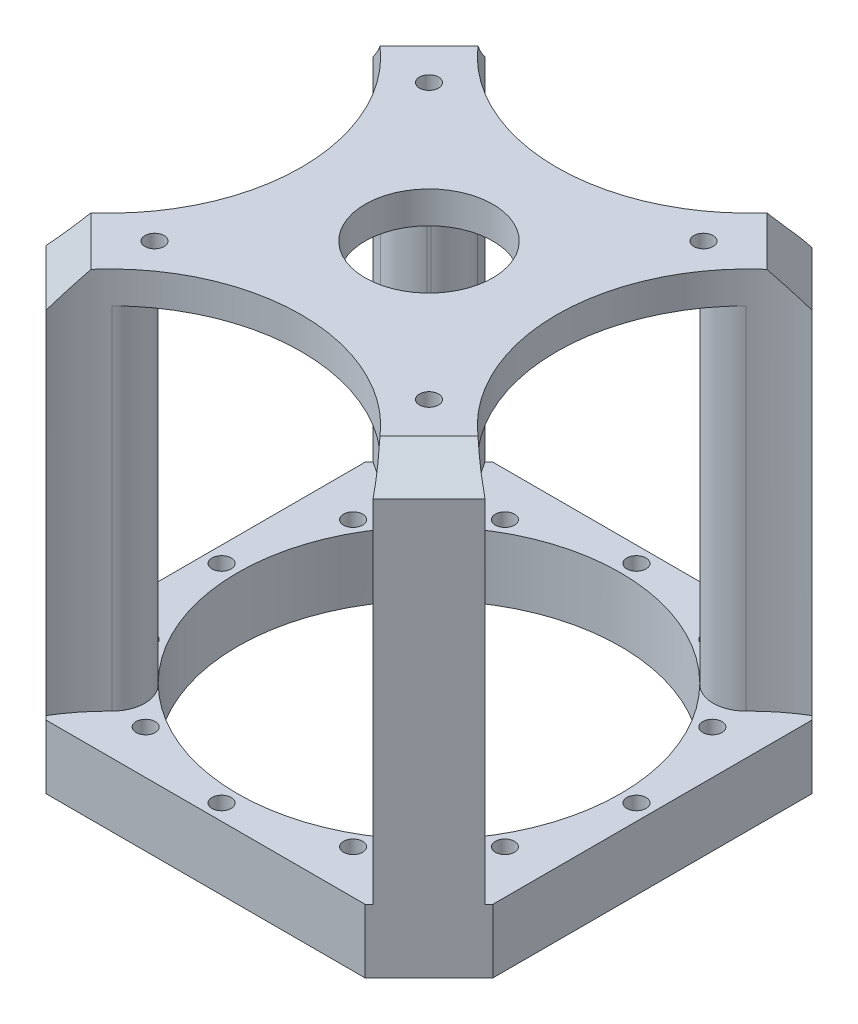
SolidWorks part; units mm, degrees
ref_plane "Front Plane" through (0, 0, 0) normal (0, 0, 1) x (1, 0, 0)
ref_plane "Top Plane" through (0, 0, 0) normal (0, 1, 0) x (1, 0, 0)
ref_plane "Right Plane" through (0, 0, 0) normal (1, 0, 0) x (0, 0, -1)
sketch "Sketch1" plane through (0, 0, 0) normal (0, 1, 0) x (1, 0, 0)
  line L1 (-35, -35) -> (35, -35)
  line L2 (-35, -35) -> (-35, 35)
  line L3 (-35, 35) -> (35, 35)
  line L4 (35, -35) -> (35, 35)
  line L5 (-35, -35) -> (35, 35) construction
  line L6 (-35, 35) -> (35, -35) construction
  circle A0 centre (0, 0) radius 35 construction
  circle A1 centre (0, 0) radius 30
  circle A2 centre (0, 0) radius 32.5 construction
  circle A3 centre (0, 32.5) radius 1.5
  circle A4 centre (16.25, 28.1458) radius 1.5
  circle A5 centre (28.1458, 16.25) radius 1.5
  circle A6 centre (32.5, 0) radius 1.5
  circle A7 centre (28.1458, -16.25) radius 1.5
  circle A8 centre (16.25, -28.1458) radius 1.5
  circle A9 centre (0, -32.5) radius 1.5
  circle A10 centre (-16.25, -28.1458) radius 1.5
  circle A11 centre (-28.1458, -16.25) radius 1.5
  circle A12 centre (-32.5, 0) radius 1.5
  circle A13 centre (-28.1458, 16.25) radius 1.5
  circle A14 centre (-16.25, 28.1458) radius 1.5
  point P35 (0, 0)
  dimension "D1" = 70
  dimension "D2" = 60
  dimension "D3" = 65
  dimension "D4" = 3
  dimension "D5" = 12
extrude "Boss-Extrude1" add sketch "Sketch1" along normal blind 65
sketch "Sketch2" plane through (0, 65, 0) normal (0, 1, 0) x (1, 0, 0)
  line L1 (-35, -35) -> (35, -35)
  line L2 (-35, -35) -> (-35, 35)
  line L3 (-35, 35) -> (35, 35)
  line L4 (35, -35) -> (35, 35)
  line L5 (-35, -35) -> (35, 35) construction
  line L6 (-35, 35) -> (35, -35) construction
  line L7 (-21.5, -21.5) -> (21.5, -21.5) construction
  line L8 (-21.5, -21.5) -> (-21.5, 21.5) construction
  line L9 (-21.5, 21.5) -> (21.5, 21.5) construction
  line L10 (21.5, -21.5) -> (21.5, 21.5) construction
  line L11 (-21.5, -21.5) -> (21.5, 21.5) construction
  line L12 (-21.5, 21.5) -> (21.5, -21.5) construction
  circle A0 centre (0, 0) radius 32.5 construction
  circle A1 centre (0, 32.5) radius 1.5
  circle A2 centre (16.25, 28.1458) radius 1.5
  circle A3 centre (28.1458, 16.25) radius 1.5
  circle A4 centre (32.5, 0) radius 1.5
  circle A5 centre (28.1458, -16.25) radius 1.5
  circle A6 centre (16.25, -28.1458) radius 1.5
  circle A7 centre (0, -32.5) radius 1.5
  circle A8 centre (-16.25, -28.1458) radius 1.5
  circle A9 centre (-28.1458, -16.25) radius 1.5
  circle A10 centre (-32.5, 0) radius 1.5
  circle A11 centre (-28.1458, 16.25) radius 1.5
  circle A12 centre (-16.25, 28.1458) radius 1.5
  circle A13 centre (0, 0) radius 10
  circle A14 centre (-21.5, 21.5) radius 1.5
  circle A15 centre (21.5, 21.5) radius 1.5
  circle A16 centre (21.5, -21.5) radius 1.5
  circle A17 centre (-21.5, -21.5) radius 1.5
  point P0 (0, 0)
  point P37 (0, 0)
  dimension "D1" = 65
  dimension "D3" = 20
  dimension "D4" = 43
  dimension "D2" = 12
extrude "Boss-Extrude2" add sketch "Sketch2" along normal blind 5
sketch "Sketch3" plane through (0, 70, 0) normal (0, 1, 0) x (1, 0, 0)
  line L0 (0, 0) -> (0, 50) construction
  circle A0 centre (0, 50) radius 30
  dimension "D2" = 60
  dimension "D1" = 50
extrude "Cut-Extrude1" cut sketch "Sketch3" against normal blind 60
pattern_circular "CirPattern1" count 4 over 360 about axis through (0, 65, 0) along (0, -1, 0) of "Cut-Extrude1" reverse direction yes
fillet "Fillet2" radius 5.1 9 edges at (25, 37.5, 16.5831) (25, 37.5, -16.5831) (-16.5831, 37.5, 25) (16.5831, 37.5, 25) (25.9808, 40, -35) (-25, 37.5, -16.5831) (-25, 37.5, 16.5831) (-16.5831, 37.5, -25) (16.5831, 37.5, -25)
chamfer "Chamfer1" distance 10 angle 45 4 edges at (35, 35, 35) (35, 35, -35) (-35, 35, -35) (-35, 35, 35)
chamfer "Chamfer2" distance 5 angle 45 4 edges at (-30, 70, 30) (30, 70, 30) (30.1385, 70, -29.8615) (-30, 70, -30)
